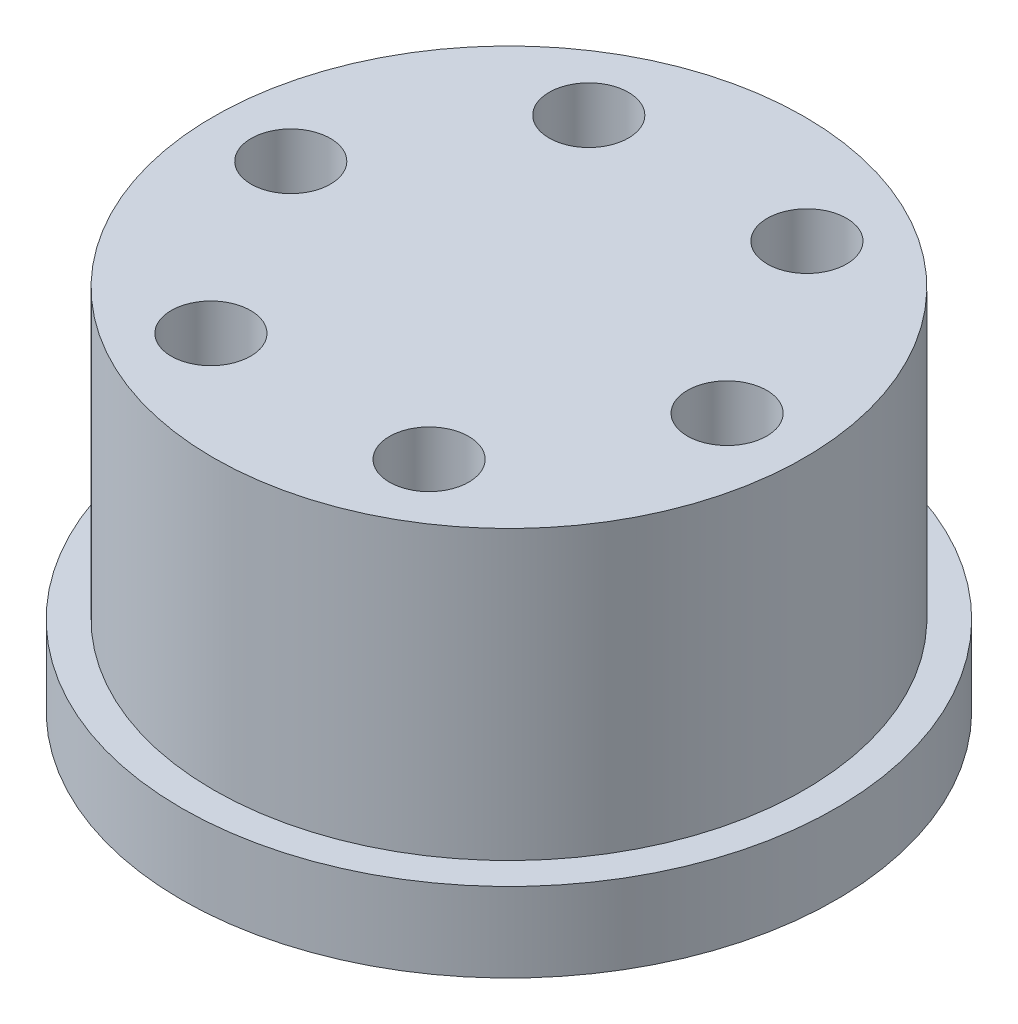
SolidWorks part; units mm, degrees
ref_plane "Front Plane" through (0, 0, 0) normal (0, 0, 1) x (1, 0, 0)
ref_plane "Top Plane" through (0, 0, 0) normal (0, 1, 0) x (1, 0, 0)
ref_plane "Right Plane" through (0, 0, 0) normal (1, 0, 0) x (0, 0, -1)
sketch "Sketch1" plane through (0, 0, 0) normal (0, 1, 0) x (1, 0, 0)
  circle A0 centre (0, 0) radius 16.5
  circle A1 centre (0, 0) radius 12.5 construction
  circle A2 centre (0, 12.5) radius 1.75
  circle A3 centre (10.8253, 6.25) radius 1.75
  circle A4 centre (10.8253, -6.25) radius 1.75
  circle A5 centre (0, -12.5) radius 1.75
  circle A6 centre (-10.8253, -6.25) radius 1.75
  circle A7 centre (-10.8253, 6.25) radius 1.75
  point P19 (0, 0)
  dimension "D1" = 33
  dimension "D2" = 25
  dimension "D3" = 3.5
  dimension "D4" = 6
extrude "Boss-Extrude1" add sketch "Sketch1" along normal blind 4
sketch "Sketch2" plane through (0, 4, 0) normal (0, 1, 0) x (1, 0, 0)
  circle A0 centre (0, 0) radius 14.9
  dimension "D1" = 29.8
extrude "Boss-Extrude2" add sketch "Sketch2" along normal blind 14.5
sketch "Sketch5" plane through (0, 18.5, 0) normal (0, 1, 0) x (1, 0, 0)
  circle A0 centre (0, 0) radius 11 construction
  circle A1 centre (-11, 0) radius 2
  circle A2 centre (-5.5, 9.5263) radius 2
  circle A3 centre (5.5, 9.5263) radius 2
  circle A4 centre (11, 0) radius 2
  circle A5 centre (5.5, -9.5263) radius 2
  circle A6 centre (-5.5, -9.5263) radius 2
  point P17 (0, 0)
  dimension "D1" = 22
  dimension "D2" = 4
  dimension "D3" = 6
extrude "Cut-Extrude3" cut sketch "Sketch5" against normal blind 6.5
sketch "Sketch6" plane through (0, 0, 0) normal (0, -1, 0) x (1, 0, 0)
  circle A0 centre (0, 0) radius 7.6
  dimension "D1" = 15.2
extrude "Cut-Extrude4" cut sketch "Sketch6" against normal blind 5
